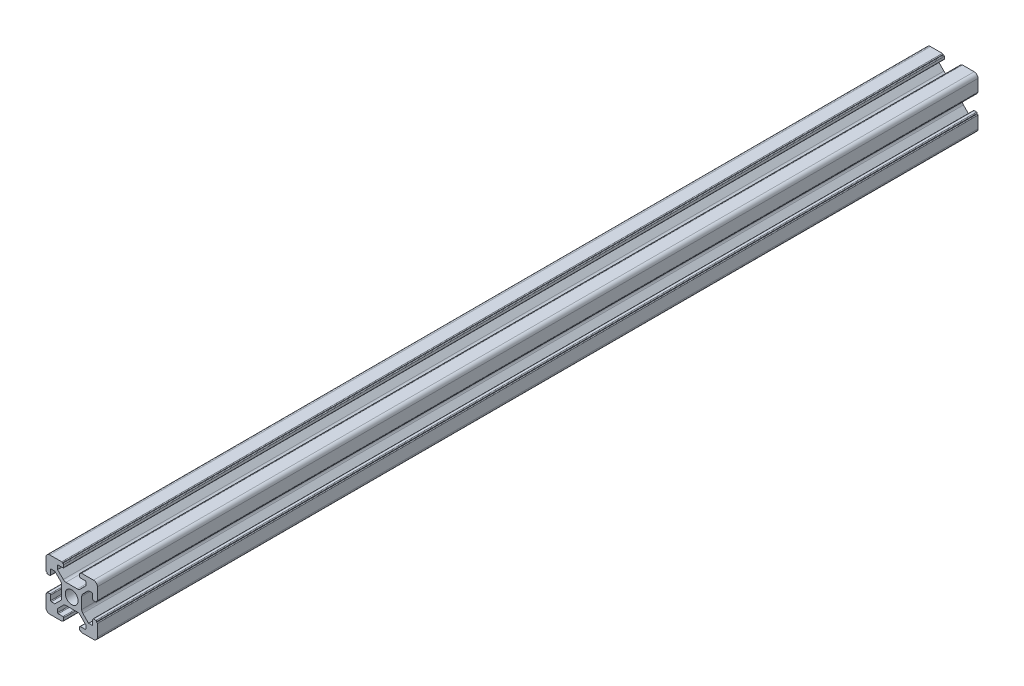
SolidWorks part; units mm, degrees
material "1060 Alloy"
ref_plane "Front Plane" through (0, 0, 0) normal (0, 0, 1) x (1, 0, 0)
ref_plane "Top Plane" through (0, 0, 0) normal (0, 1, 0) x (1, 0, 0)
ref_plane "Right Plane" through (0, 0, 0) normal (1, 0, 0) x (0, 0, -1)
sketch "Sketch1" plane through (0, 0, 0) normal (0, 0, 1) x (1, 0, 0)
  line L0 (3.8995, 3.9005) -> (10.4604, 10.4604) construction
  line L2 (-3.9002, 2.2177) -> (-3.9002, -2.2208)
  line L5 (-3.9005, 3.899) -> (3.9001, -3.8986) construction
  line L6 (-3.9, -3.901) -> (3.8995, 3.9005) construction
  line L7 (-0.0002, 10) -> (-0.0002, -9.9996) construction
  line L8 (-0.0002, -9.9996) -> (-0.0002, 10) construction
  line L9 (5.5006, 6.5619) -> (3.2793, 4.3405)
  line L14 (-10.0002, 9.9996) -> (9.9994, -10) construction
  line L15 (-9.9999, -10.0001) -> (9.9998, 10) construction
  line L16 (6.5613, 5.5012) -> (4.3401, 3.28)
  line L17 (-5.5002, 6.5603) -> (-3.279, 4.3391)
  line L18 (-6.5609, 5.4996) -> (-4.3395, 3.2783)
  line L19 (7.9206, 5.5012) -> (6.5613, 5.5012)
  line L20 (8.2006, 3.3812) -> (8.2006, 5.2212)
  line L21 (9.4206, 3.1012) -> (8.4806, 3.1012)
  line L22 (9.7006, 3.6012) -> (9.7006, 3.3812)
  line L23 (-8.5002, 9.9996) -> (-3.8802, 9.9996)
  line L24 (-3.6002, 9.7196) -> (-3.6002, 9.6996)
  line L25 (-3.6002, 9.6996) -> (-3.3802, 9.6996)
  line L26 (-3.1002, 9.4196) -> (-3.1002, 8.4796)
  line L27 (-3.3802, 8.1996) -> (-5.2202, 8.1996)
  line L28 (-5.5002, 7.9196) -> (-5.5002, 6.5603)
  line L29 (-7.9202, 5.4996) -> (-6.5609, 5.4996)
  line L30 (-8.2002, 3.3796) -> (-8.2002, 5.2196)
  line L31 (-9.4202, 3.0996) -> (-8.4802, 3.0996)
  line L32 (-9.7202, 3.5996) -> (-9.7002, 3.5996)
  line L33 (-9.7002, 3.5996) -> (-9.7002, 3.3796)
  line L34 (-10.0002, 8.4996) -> (-10.0002, 3.8796)
  line L35 (10.0006, 8.5012) -> (10.0006, 3.8812)
  line L36 (8.5006, 10.0012) -> (3.8806, 10.0012)
  line L37 (3.6006, 9.7012) -> (3.3806, 9.7012)
  line L38 (3.1006, 9.4212) -> (3.1006, 8.4812)
  line L39 (3.3806, 8.2012) -> (5.2206, 8.2012)
  line L40 (5.5006, 7.9212) -> (5.5006, 6.5619)
  line L41 (6.5629, -5.4996) -> (4.3415, -3.2783)
  line L42 (5.5022, -6.5603) -> (3.281, -4.3391)
  line L43 (5.5022, -7.9196) -> (5.5022, -6.5603)
  line L44 (3.3822, -8.1996) -> (5.2222, -8.1996)
  line L45 (3.1022, -9.4196) -> (3.1022, -8.4796)
  line L46 (3.6022, -9.6996) -> (3.3822, -9.6996)
  line L47 (8.5022, -9.9996) -> (3.8822, -9.9996)
  line L48 (10.0022, -8.4996) -> (10.0022, -3.8796)
  line L49 (9.7022, -3.5996) -> (9.7022, -3.3796)
  line L50 (9.4222, -3.0996) -> (8.4822, -3.0996)
  line L51 (8.2022, -3.3796) -> (8.2022, -5.2196)
  line L52 (7.9222, -5.4996) -> (6.5629, -5.4996)
  line L53 (-5.4986, -6.5619) -> (-3.2773, -4.3405)
  line L54 (-6.5593, -5.5012) -> (-4.3395, -3.2814)
  line L55 (-7.9186, -5.5012) -> (-6.5593, -5.5012)
  line L56 (-8.1986, -3.3812) -> (-8.1986, -5.2212)
  line L57 (-9.4186, -3.1012) -> (-8.4786, -3.1012)
  line L58 (-9.6986, -3.6012) -> (-9.6986, -3.3812)
  line L59 (-9.9986, -8.5012) -> (-9.9986, -3.8812)
  line L60 (-8.4986, -10.0012) -> (-3.8786, -10.0012)
  line L61 (-3.5986, -9.7012) -> (-3.3786, -9.7012)
  line L62 (-3.0986, -9.4212) -> (-3.0986, -8.4812)
  line L63 (-3.3786, -8.2012) -> (-5.2186, -8.2012)
  line L64 (-5.4986, -7.9212) -> (-5.4986, -6.5619)
  line L65 (-2.233, 3.8998) -> (2.2187, 3.9012)
  line L66 (3.9008, 2.234) -> (3.9022, -2.2177)
  line L67 (2.235, -3.8998) -> (-2.2167, -3.9012)
  line L68 (3.6006, 9.7212) -> (3.6006, 9.6996)
  line L69 (9.7006, 3.6012) -> (9.7206, 3.6012)
  line L70 (-9.6986, -3.6012) -> (-9.7186, -3.6012)
  line L71 (-3.5986, -9.7012) -> (-3.5986, -9.7212)
  line L72 (3.6022, -9.6996) -> (3.6022, -9.7196)
  line L73 (9.7222, -3.5996) -> (9.7022, -3.5996)
  arc A0 (-3.6002, 9.7196) -> (-3.8802, 9.9996) centre (-3.8802, 9.7196) ccw
  arc A1 (-3.3802, 9.6996) -> (-3.1002, 9.4196) centre (-3.3802, 9.4196) cw
  arc A2 (-3.1002, 8.4796) -> (-3.3802, 8.1996) centre (-3.3802, 8.4796) cw
  arc A3 (-10.0002, 8.4996) -> (-8.5002, 9.9996) centre (-8.5002, 8.4996) cw
  arc A4 (-8.2002, 3.3796) -> (-8.4802, 3.0996) centre (-8.4802, 3.3796) cw
  arc A5 (-9.4202, 3.0996) -> (-9.7002, 3.3796) centre (-9.4202, 3.3796) cw
  arc A6 (-9.7202, 3.5996) -> (-10.0002, 3.8796) centre (-9.7202, 3.8796) cw
  arc A7 (-3.279, 4.3391) -> (-2.233, 3.8998) centre (-2.2183, 5.3997) ccw
  arc A8 (-4.3395, 3.2783) -> (-3.9002, 2.2177) centre (-5.4002, 2.2177) cw
  arc A9 (-7.9202, 5.4996) -> (-8.2002, 5.2196) centre (-7.9202, 5.2196) ccw
  arc A10 (-5.2202, 8.1996) -> (-5.5002, 7.9196) centre (-5.2202, 7.9196) ccw
  arc A12 (-4.3395, -3.2814) -> (-3.9002, -2.2208) centre (-5.4002, -2.2208) ccw
  arc A13 (8.2006, 5.2212) -> (7.9206, 5.5012) centre (7.9206, 5.2212) ccw
  arc A14 (8.4806, 3.1012) -> (8.2006, 3.3812) centre (8.4806, 3.3812) cw
  arc A15 (9.7006, 3.3812) -> (9.4206, 3.1012) centre (9.4206, 3.3812) cw
  arc A16 (9.7206, 3.6012) -> (10.0006, 3.8812) centre (9.7206, 3.8812) ccw
  arc A17 (8.5006, 10.0012) -> (10.0006, 8.5012) centre (8.5006, 8.5012) cw
  arc A18 (3.6006, 9.7212) -> (3.8806, 10.0012) centre (3.8806, 9.7212) cw
  arc A19 (3.1006, 9.4212) -> (3.3806, 9.7012) centre (3.3806, 9.4212) cw
  arc A20 (3.3806, 8.2012) -> (3.1006, 8.4812) centre (3.3806, 8.4812) cw
  arc A21 (5.5006, 7.9212) -> (5.2206, 8.2012) centre (5.2206, 7.9212) ccw
  arc A22 (3.2793, 4.3405) -> (2.2187, 3.9012) centre (2.2187, 5.4012) cw
  arc A23 (4.3401, 3.28) -> (3.9008, 2.234) centre (5.4007, 2.2193) ccw
  arc A25 (5.2222, -8.1996) -> (5.5022, -7.9196) centre (5.2222, -7.9196) ccw
  arc A26 (3.1022, -8.4796) -> (3.3822, -8.1996) centre (3.3822, -8.4796) cw
  arc A27 (3.3822, -9.6996) -> (3.1022, -9.4196) centre (3.3822, -9.4196) cw
  arc A28 (3.6022, -9.7196) -> (3.8822, -9.9996) centre (3.8822, -9.7196) ccw
  arc A29 (10.0022, -8.4996) -> (8.5022, -9.9996) centre (8.5022, -8.4996) cw
  arc A30 (9.7222, -3.5996) -> (10.0022, -3.8796) centre (9.7222, -3.8796) cw
  arc A31 (9.4222, -3.0996) -> (9.7022, -3.3796) centre (9.4222, -3.3796) cw
  arc A32 (8.2022, -3.3796) -> (8.4822, -3.0996) centre (8.4822, -3.3796) cw
  arc A33 (7.9222, -5.4996) -> (8.2022, -5.2196) centre (7.9222, -5.2196) ccw
  arc A34 (4.3415, -3.2783) -> (3.9022, -2.2177) centre (5.4022, -2.2177) cw
  arc A35 (3.281, -4.3391) -> (2.235, -3.8998) centre (2.2203, -5.3997) ccw
  circle A36 centre (0.001, -0.001) radius 2.5 construction
  arc A37 (-8.1986, -5.2212) -> (-7.9186, -5.5012) centre (-7.9186, -5.2212) ccw
  arc A38 (-8.4786, -3.1012) -> (-8.1986, -3.3812) centre (-8.4786, -3.3812) cw
  arc A39 (-9.6986, -3.3812) -> (-9.4186, -3.1012) centre (-9.4186, -3.3812) cw
  arc A40 (-9.7186, -3.6012) -> (-9.9986, -3.8812) centre (-9.7186, -3.8812) ccw
  arc A41 (-8.4986, -10.0012) -> (-9.9986, -8.5012) centre (-8.4986, -8.5012) cw
  arc A42 (-3.5986, -9.7212) -> (-3.8786, -10.0012) centre (-3.8786, -9.7212) cw
  arc A43 (-3.0986, -9.4212) -> (-3.3786, -9.7012) centre (-3.3786, -9.4212) cw
  arc A44 (-3.3786, -8.2012) -> (-3.0986, -8.4812) centre (-3.3786, -8.4812) cw
  arc A45 (-5.4986, -7.9212) -> (-5.2186, -8.2012) centre (-5.2186, -7.9212) ccw
  arc A46 (-3.2773, -4.3405) -> (-2.2167, -3.9012) centre (-2.2167, -5.4012) cw
  arc A48 (-4.3381, -3.28) -> (-3.8988, -2.234) centre (-5.3987, -2.2193) ccw [skipped]
  point P0 (0, 0)
  point P9 (-0.0002, 0.0002)
  point P12 (-0.0003, -0.0003)
  point P43 (-3.6002, 9.9996)
  point P46 (-3.1002, 9.6996)
  point P49 (-3.1002, 8.1996)
  point P55 (-8.2002, 3.0996)
  point P58 (-9.7002, 3.0996)
  point P61 (-10.0002, 3.5996)
  point P64 (-2.8395, 3.8996)
  point P67 (-3.9002, 2.839)
  point P70 (-8.2002, 5.4996)
  point P73 (-5.5002, 8.1996)
  point P184 (0.001, 0)
  dimension "D14" = 0.28
  dimension "D15" = 0.28
  dimension "D16" = 0.28
  dimension "D17" = 1.5
  dimension "D18" = 0.28
  dimension "D19" = 1.5
  dimension "D20" = 1.5
  dimension "D21" = 0.28
  dimension "D23" = 5
  dimension "D27" = 1.5
  dimension "D1" = 7.8
  dimension "D2" = 7.8
  dimension "D3" = 3.1
  dimension "D4" = 3.6
  dimension "D5" = 20
  dimension "D6" = 20
  dimension "D7" = 0.75
  dimension "D8" = 1.8
  dimension "D9" = 5.5
  dimension "D10" = 6.4
  dimension "D11" = 6.4
  dimension "D12" = 3.7627
  dimension "D13" = 0.3
  dimension "D24" = 4.62
  dimension "D25" = 3.9005
  dimension "D26" = 7.801
  dimension "D22" = 4
extrude "Boss-Extrude1" add sketch "Sketch1" along normal blind 342.9 contours L53 A46 L67 A35 L42 L43 A25 L44 A26 L45 A27 L46 L72 A28 L47 A29 L48 A30 L73 L49 A31 L50 A32 L51 A33 L52 L41 A34 L66 A23 L16 L19 A13 L20 A14 L21 A15 L22 L69 A16 L35 A17 L36 A18 L68 L37 A19 L38 A20 region at (0.0009, 0, 0)
sketch3d "3DSketch2"
  circle A0 centre (0, 0, 0) radius 2.5
  point P2 (0, 0, 2.5)
extrude "Cut-Extrude1" cut sketch "3DSketch2" along direction (0, 0, 1) on the side of the normal through all contours A0
